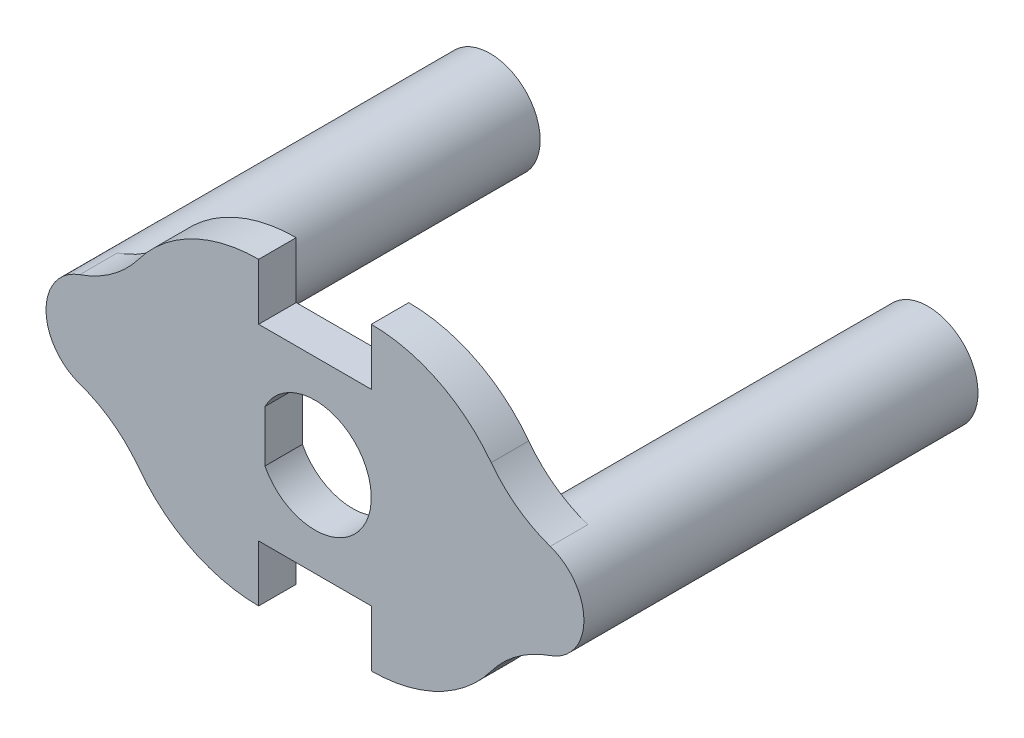
SolidWorks part; units mm, degrees
ref_plane "前视基准面" through (0, 0, 0) normal (0, 0, 1) x (1, 0, 0)
ref_plane "上视基准面" through (0, 0, 0) normal (0, 1, 0) x (1, 0, 0)
ref_plane "右视基准面" through (0, 0, 0) normal (1, 0, 0) x (0, 0, -1)
sketch "草图1" plane through (0, 0, 0) normal (0, 0, 1) x (1, 0, 0)
  line L0 (0, 0) -> (23.5174, 0) construction
  line L1 (0, 0) -> (0, 15) construction
  line L2 (-4.5, 7.5) -> (4.5, 7.5)
  line L3 (4.5, 7.5) -> (4.5, 12)
  line L4 (-4.5, 7.5) -> (-4.5, 12)
  line L5 (4.5, -7.5) -> (4.5, -12)
  line L6 (-4.5, -7.5) -> (4.5, -7.5)
  line L7 (-4.5, -7.5) -> (-4.5, -12)
  arc A0 (4.5, 12) -> (14.0874, 7.2168) centre (4.5, 0) cw
  arc A1 (18.8077, -3.7802) -> (18.8077, 3.7802) centre (17.5, 0) ccw
  arc A2 (14.0874, 7.2168) -> (18.8077, 3.7802) centre (22.0769, 13.2307) ccw
  arc A3 (-14.0874, 7.2168) -> (-18.8077, 3.7802) centre (-22.0769, 13.2307) cw
  arc A4 (-4.5, 12) -> (-14.0874, 7.2168) centre (-4.5, 0) ccw
  arc A5 (14.0874, -7.2168) -> (18.8077, -3.7802) centre (22.0769, -13.2307) cw
  arc A6 (4.5, -12) -> (14.0874, -7.2168) centre (4.5, 0) ccw
  arc A7 (-4.5, -12) -> (-14.0874, -7.2168) centre (-4.5, 0) cw
  arc A8 (-14.0874, -7.2168) -> (-18.8077, -3.7802) centre (-22.0769, -13.2307) ccw
  arc A9 (-18.8077, -3.7802) -> (-18.8077, 3.7802) centre (-17.5, 0) cw
  point P22 (0, 7.5)
  dimension "D1" = 7.5
  dimension "D2" = 8
  dimension "D6" = 12
  dimension "D7" = 10
  dimension "D3" = 4.5
  dimension "D4" = 17.5
  dimension "D5" = 4.5
extrude "凸台-拉伸1" add sketch "草图1" against normal mid plane 3
sketch "草图4" plane through (0, 0, 1.5) normal (0, 0, 1) x (1, 0, 0)
  line L0 (-4, 2.0616) -> (-4, -2.0616)
  arc A0 (-4, -2.0616) -> (-4, 2.0616) centre (0, 0) ccw
  dimension "D1" = 9
  dimension "4" = 4
extrude "切除-拉伸1" cut sketch "草图4" against normal through all
sketch "草图5" plane through (0, 0, -1.5) normal (0, 0, -1) x (-1, 0, 0)
  circle A0 centre (-17.5, 0) radius 4
  arc A1 (-18.8077, 3.7802) -> (-18.8077, -3.7802) centre (-17.5, 0) ccw construction
extrude "凸台-拉伸2" add sketch "草图5" along normal blind 28.5
sketch "草图8" plane through (0, 0, -30) normal (0, 0, -1) x (-1, 0, 0)
  circle A0 centre (-17.5, 0) radius 1.5
  dimension "D1" = 3
extrude "切除-拉伸2" cut sketch "草图8" against normal blind 10.5
mirror "镜向2" about plane through (0, 0, 0) normal (1, 0, 0) of "切除-拉伸2", "凸台-拉伸2"
ref_plane "基准面8" through (0, 0, -15.5) normal (0, 0, -1) x (-1, 0, 0)
sketch "草图10" plane through (0, 0, -15.5) normal (0, 0, -1) x (-1, 0, 0)
  line L0 (20.0884, -3.0496) -> (20.0884, 3.0496)
  circle A0 centre (17.5, 0) radius 4 construction
  arc A1 (20.0884, -3.0496) -> (20.0884, 3.0496) centre (17.5, 0) ccw
  dimension "D1" = 6.0992
extrude "切除-拉伸3" cut sketch "草图10" against normal blind 9 and the other way blind 6
ref_plane "基准面9" through (-20.0884, 0, 0) normal (-1, 0, 0) x (0, 0, 1)
sketch "草图14" plane through (-20.0884, 0, 0) normal (-1, 0, 0) x (0, 0, 1)
  line L0 (-30, 4) -> (-30, -4) construction
  line L3 (-30, -4) -> (-1.5, -4) construction
  circle A0 centre (-16.5, 0) radius 1.5
  circle A1 centre (-10.5, 0) radius 1.5
  point P4 (0, 0)
  dimension "D1" = 3
  dimension "D4" = 3
  dimension "D5" = 3
  dimension "D2" = 13.5
  dimension "D3" = 4
extrude "切除-拉伸4" cut sketch "草图14" against normal blind 5
ref_axis "基准轴1" through (-15.0884, 0, -16.5) along (-1, 0, 0)
